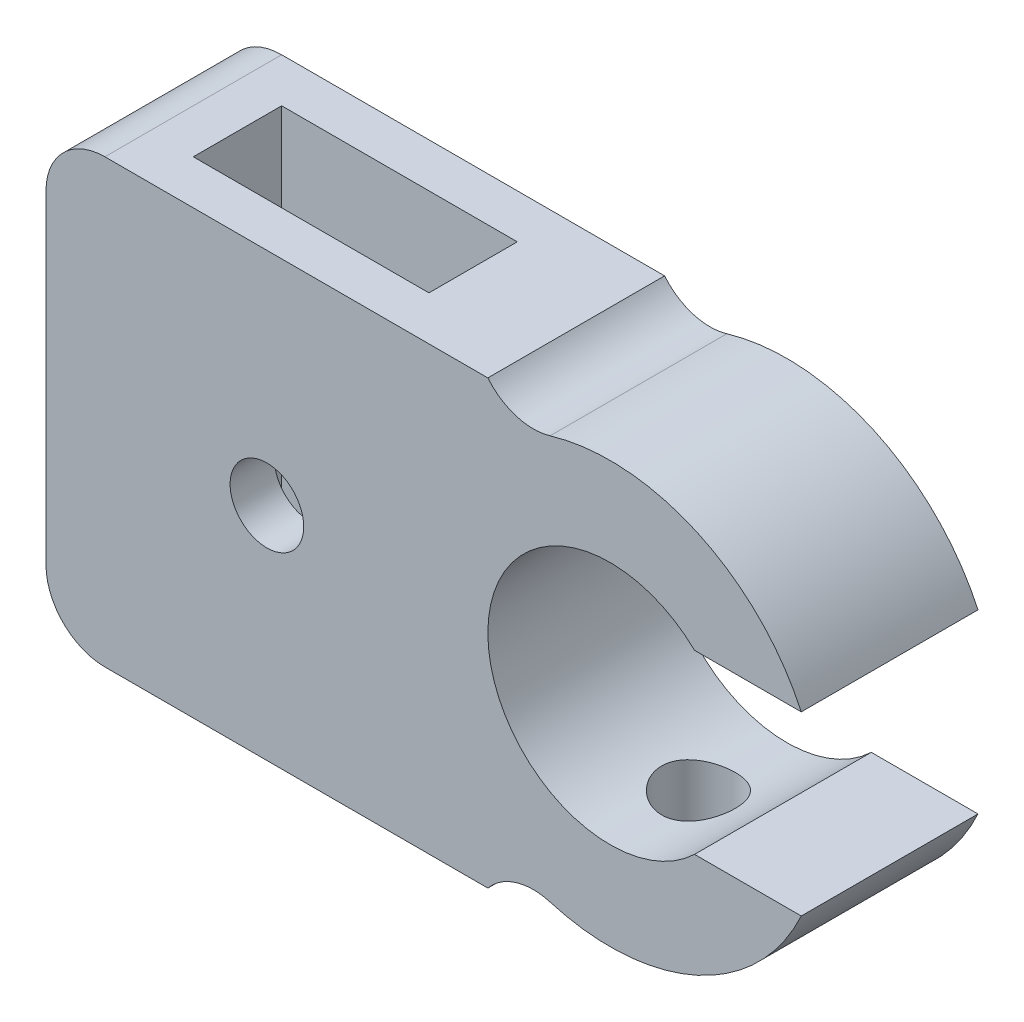
SolidWorks part; units mm, degrees
ref_plane "Front" through (0, 0, 0) normal (0, 0, 1) x (1, 0, 0)
ref_plane "Top" through (0, 0, 0) normal (0, 1, 0) x (1, 0, 0)
ref_plane "Right" through (0, 0, 0) normal (1, 0, 0) x (0, 0, -1)
sketch "Sketch1" plane through (0, 0, 0) normal (0, 0, 1) x (1, 0, 0)
  line L1 (-7.5, -7.5) -> (7.5, -7.5)
  line L2 (-7.5, -7.5) -> (-7.5, 7.5)
  line L3 (-7.5, 7.5) -> (7.5, 7.5)
  line L4 (7.5, -7.5) -> (7.5, 7.5)
  line L5 (-7.5, -7.5) -> (7.5, 7.5) construction
  line L6 (-7.5, 7.5) -> (7.5, -7.5) construction
  point P0 (0, 0)
  dimension "D1" = 15
  dimension "D2" = 15
extrude "Boss-Extrude1" add sketch "Sketch1" along normal mid plane 6
sketch "Sketch2" plane through (0, -7.5, 0) normal (0, -1, 0) x (1, 0, 0)
  line L1 (-4, -1.5) -> (4, -1.5)
  line L2 (-4, -1.5) -> (-4, 1.5)
  line L3 (-4, 1.5) -> (4, 1.5)
  line L4 (4, -1.5) -> (4, 1.5)
  line L5 (-4, -1.5) -> (4, 1.5) construction
  line L6 (-4, 1.5) -> (4, -1.5) construction
  point P0 (0, 0)
  dimension "D1" = 8
  dimension "D2" = 3
extrude "Cut-Extrude1" cut sketch "Sketch2" against normal through all
sketch "Sketch3" plane through (0, 0, 3) normal (0, 0, 1) x (1, 0, 0)
  line L0 (7.5, -7.5) -> (7.5, 7.5) construction
  line L1 (7.5, -5.8224) -> (7.5, 5.8224)
  circle A0 centre (11.65, 0) radius 4.15 construction
  arc A1 (7.5, -5.8224) -> (7.5, 5.8224) centre (11.65, 0) ccw
  circle A2 centre (11.65, 0) radius 7.15 construction
  dimension "D1" = 8.3
  dimension "D2" = 3
extrude "Boss-Extrude2" add sketch "Sketch3" against normal blind 6
fillet "Fillet1" radius 2 4 edges at (-7.5, -7.5, 0) (-7.5, 7.5, 0) (7.5, 5.8224, 0) (7.5, -5.8224, 0)
sketch "Sketch4" plane through (0, 0, -3) normal (0, 0, -1) x (-1, 0, 0)
  line L1 (-18.8, 3) -> (-14.5175, 3)
  line L2 (-18.8, 3) -> (-18.8, -3)
  line L3 (-18.8, -3) -> (-14.5175, -3)
  arc A0 (-14.5175, -3) -> (-14.5175, 3) centre (-11.65, 0) ccw
  arc A1 (-9.6137, 6.8539) -> (-9.6137, -6.8539) centre (-11.65, 0) ccw construction
  point P1 (-18.8, 0)
  dimension "D1" = 8.3
  dimension "D2" = 6
extrude "Cut-Extrude2" cut sketch "Sketch4" against normal through all contours L2 L3 A0 L1
hole_wizard "M3x0.5 Tapped Hole1" positions "Sketch6" profile "Sketch5" tap size "M3x0.5" standard "ANSI Metric"
sketch "Sketch6" plane through (0, -7.5, 0) normal (0, -1, 0) x (-1, 0, 0)
  line L0 (7.5, 3) -> (7.5, -3) construction
  point P0 (-11.65, 0)
  dimension "D1" = 19.15
sketch "Sketch5" plane through (11.65, -7.5, 0) normal (1, 0, 0) x (0, 0, -1)
  line L0 (0, 0) -> (0, 8.2511)
  line L1 (0, 8.2511) -> (1.25, 7.5)
  line L2 (1.25, 7.5) -> (1.25, 0)
  line L5 (1.25, 0) -> (0, 0)
  line L10 (0, 8.2511) -> (-1.25, 7.5) construction
  line L11 (0, -6.35) -> (0, 107.95) construction
  dimension "Tap Drill Dia." = 2.5
  dimension "Tap Drill Depth" = 7.5
  dimension "Drill Angle" = 118
hole_wizard "M3x0.5 Tapped Hole2" positions "Sketch8" profile "Sketch7" tap size "M3x0.5" standard "ANSI Metric"
sketch "Sketch8" plane through (0, 0, 3) normal (0, 0, 1) x (1, 0, 0)
  point P0 (0, 0)
sketch "Sketch7" plane through (0, 0, 3) normal (1, 0, 0) x (0, -1, 0)
  line L0 (0, 0) -> (0, 8.2511)
  line L1 (0, 8.2511) -> (1.25, 7.5)
  line L2 (1.25, 7.5) -> (1.25, 0)
  line L5 (1.25, 0) -> (0, 0)
  line L10 (0, 8.2511) -> (-1.25, 7.5) construction
  line L11 (0, -6.35) -> (0, 107.95) construction
  dimension "Tap Drill Dia." = 2.5
  dimension "Tap Drill Depth" = 7.5
  dimension "Drill Angle" = 118
